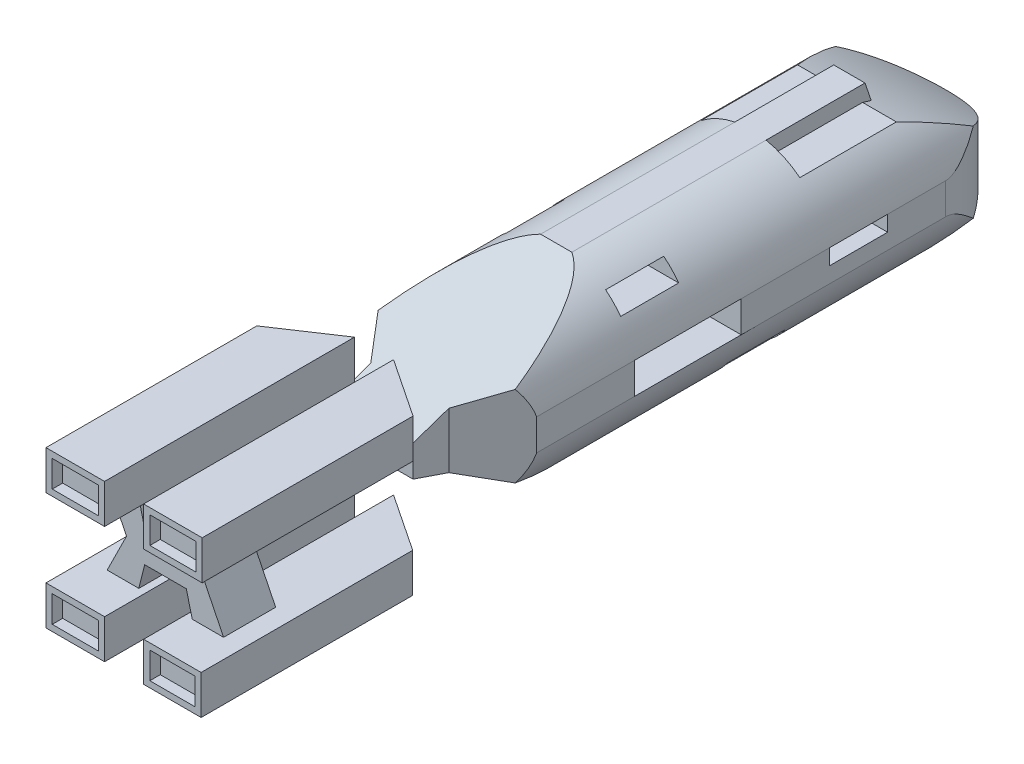
SolidWorks part; units mm, degrees
material "Ti-8Mn annealed sheet (SS)"
ref_plane "Front Plane" through (0, 0, 0) normal (0, 0, 1) x (1, 0, 0)
ref_plane "Top Plane" through (0, 0, 0) normal (0, 1, 0) x (1, 0, 0)
ref_plane "Right Plane" through (0, 0, 0) normal (1, 0, 0) x (0, 0, -1)
sketch "Sketch1" plane through (0, 0, 0) normal (0, 1, 0) x (1, 0, 0)
  line L1 (-75000, 375000) -> (75000, 375000)
  line L2 (-75000, 375000) -> (-75000, -375000)
  line L3 (-75000, -375000) -> (75000, -375000)
  line L4 (75000, 375000) -> (75000, -375000)
  line L5 (-75000, 375000) -> (75000, -375000) construction
  line L6 (-75000, -375000) -> (75000, 375000) construction
  point P0 (0, 0)
  dimension "D1" = 150000
  dimension "D2" = 750000
extrude "Boss-Extrude1" add sketch "Sketch1" along normal blind 150000
sketch "Sketch3" plane through (75000, 0, 0) normal (1, 0, 0) x (0, 0, -1)
  line L0 (0, -5407.3313) -> (0, 150000) construction
  line L1 (-375000, 150000) -> (375000, 150000) construction
  line L2 (187500, 150000) -> (375000, 150000)
  line L3 (375000, 150000) -> (375000, 90000)
  line L4 (187500, 150000) -> (187500, 0) construction
  line L5 (-375000, 0) -> (375000, 0) construction
  line L6 (375000, 60000) -> (375000, 0)
  line L7 (375000, 0) -> (187500, 0)
  line L8 (375000, 150000) -> (375000, 0) construction
  line L12 (187500, 150000) -> (187500, 0) construction
  line L19 (375000, 75000) -> (375000, 90000) construction
  line L20 (375000, 90000) -> (375000, 75000) construction
  line L21 (375000, 75000) -> (375000, 60000) construction
  arc A0 (375000, 90000) -> (187500, 150000) centre (175711.7775, -209806.9452) ccw
  arc A1 (375000, 60000) -> (187500, 0) centre (175711.7775, 359806.9452) cw
  dimension "D1" = 15000
  dimension "D2" = 15000
extrude "Cut-Extrude2" cut sketch "Sketch3" against normal through all
sketch "Sketch4" plane through (0, 150000, 0) normal (0, 1, 0) x (1, 0, 0)
  line L0 (0, 0) -> (0, -375000) construction
  line L1 (-75000, -375000) -> (75000, -375000) construction
  line L2 (0, -375000) -> (0, -187500) construction
  line L3 (0, -187500) -> (0, 0) construction
  line L4 (0, -187500) -> (-75000, -187500) construction
  line L5 (-75000, 187500) -> (-75000, -375000) construction
  line L6 (-75000, -187500) -> (75000, -187500) construction
  line L7 (75000, -375000) -> (75000, 187500) construction
  line L8 (75000, -187500) -> (75000, -93750) construction
  line L9 (75000, -93750) -> (-75000, -93750) construction
  line L10 (-75000, -93750) -> (-75000, -187500) construction
  line L11 (-37500, -187500) -> (-37500, -93750) construction
  line L12 (-37500, -93750) -> (0, -187500) construction
  line L13 (0, -187500) -> (75000, -187500) construction
  line L14 (75000, -187500) -> (37500, -187500) construction
  line L15 (37500, -187500) -> (37500, -93750) construction
  line L16 (37500, -93750) -> (0, -187500) construction
  line L17 (-75000, -93750) -> (-37500, -140625)
  line L18 (-37500, -140625) -> (-37500, -187500)
  line L19 (-37500, -187500) -> (-75000, -187500)
  line L20 (-75000, -187500) -> (-75000, -93750)
  line L21 (75000, -93750) -> (37500, -140625)
  line L22 (37500, -140625) -> (37500, -187500)
  line L23 (37500, -187500) -> (75000, -187500)
  line L24 (75000, -187500) -> (75000, -93750)
extrude "Cut-Extrude3" cut sketch "Sketch4" against normal through all
sketch "Sketch5" plane through (0, 0, 375000) normal (0, 0, 1) x (1, 0, 0)
  line L0 (0, 0) -> (0, 150000) construction
  line L1 (-75000, 0) -> (75000, 0) construction
  line L2 (-75000, 150000) -> (75000, 150000) construction
  line L3 (0, 150000) -> (0, 75000) construction
  line L4 (0, 75000) -> (75000, 150000) construction
  line L5 (75000, 150000) -> (75000, 75000) construction
  line L6 (75000, 150000) -> (75000, 0) construction
  line L7 (75000, 75000) -> (75000, 0) construction
  line L8 (75000, 0) -> (0, 75000) construction
  line L9 (0, 75000) -> (-75000, 150000) construction
  line L10 (-75000, 150000) -> (-75000, 75000) construction
  line L11 (-75000, 150000) -> (-75000, 0) construction
  line L12 (-75000, 75000) -> (-75000, 0) construction
  line L13 (-75000, 0) -> (0, 75000) construction
  line L14 (-37500, 112500) -> (0, 112500) construction
  line L15 (0, 112500) -> (37500, 112500) construction
  line L16 (37500, 112500) -> (18750, 112500) construction
  line L17 (18750, 112500) -> (18750, 0) construction
  line L18 (18750, 0) -> (-18750, 0) construction
  line L19 (-18750, 0) -> (-18750, 112500) construction
  line L20 (-75000, 150000) -> (-18750, 150000)
  line L21 (-75000, 150000) -> (-75000, 112500)
  line L22 (-18750, 150000) -> (-18750, 112500)
  line L23 (-75000, 112500) -> (-18750, 112500)
  line L24 (18750, 112500) -> (75000, 112500)
  line L25 (18750, 112500) -> (18750, 150000)
  line L26 (75000, 112500) -> (75000, 150000)
  line L27 (18750, 150000) -> (75000, 150000)
  line L28 (-75000, 37500) -> (-75000, 0)
  line L29 (-75000, 37500) -> (-18750, 37500)
  line L30 (-75000, 0) -> (-18750, 0)
  line L31 (-18750, 37500) -> (-18750, 0)
  line L32 (18750, 0) -> (18750, 37500)
  line L33 (18750, 0) -> (73969.9506, 0)
  line L34 (18750, 37500) -> (73969.9506, 37500)
  line L35 (73969.9506, 0) -> (73969.9506, 37500)
extrude "Cut-Extrude4" cut sketch "Sketch5" against normal blind 200000 flip side to cut
sketch "Sketch6" plane through (0, 0, 375000) normal (0, 0, 1) x (1, 0, 0)
  line L0 (60164.9629, 28125) -> (37113.7315, 75000)
  line L1 (-75000, 112500) -> (-75000, 37500) construction
  line L2 (-37628.7562, 75000) -> (-60937.5, 121875)
  line L3 (-18750, 0) -> (18750, 0) construction
  line L4 (-60937.5, 121875) -> (-32812.5, 140625)
  line L5 (73969.9506, 37500) -> (75000, 112500) construction
  line L6 (-37628.7562, 75000) -> (-60937.5, 28125)
  line L7 (37113.7315, 75000) -> (60937.5, 121875)
  line L8 (-75000, 75000) -> (-257.5124, 75000) construction
  line L10 (-46875, 131250) -> (46359.9753, 18750) construction
  line L11 (-257.5124, 75000) -> (-37628.7562, 75000) construction
  line L12 (-37628.7562, 75000) -> (-257.5124, 75000) construction
  line L13 (-257.5124, 75000) -> (74484.9753, 75000) construction
  line L14 (74484.9753, 75000) -> (37113.7315, 75000) construction
  line L15 (37113.7315, 75000) -> (-257.5124, 75000) construction
  line L16 (-18750, 150000) -> (-46875, 131250) construction
  line L17 (-46875, 131250) -> (-75000, 112500) construction
  line L18 (-75000, 112500) -> (-75000, 75000) construction
  line L19 (-75000, 75000) -> (-75000, 37500) construction
  line L20 (-75000, 37500) -> (-46875, 18750) construction
  line L21 (-46875, 18750) -> (-18750, 0) construction
  line L22 (-18750, 0) -> (18750, 0) construction
  line L23 (18750, 0) -> (46359.9753, 18750) construction
  line L24 (46359.9753, 18750) -> (73969.9506, 37500) construction
  line L25 (73969.9506, 37500) -> (74484.9753, 75000) construction
  line L26 (74484.9753, 75000) -> (75000, 112500) construction
  line L27 (75000, 112500) -> (46875, 131250) construction
  line L28 (46875, 131250) -> (18750, 150000) construction
  line L30 (-32812.5, 140625) -> (-20257.5124, 90000)
  line L31 (-20257.5124, 90000) -> (19742.4876, 90000)
  line L33 (-20257.5124, 60000) -> (19742.4876, 60000)
  line L35 (-20257.5124, 90000) -> (19742.4876, 60000) construction
  line L36 (-20257.5124, 60000) -> (19742.4876, 90000) construction
  line L38 (19742.4876, 90000) -> (32812.5, 140625)
  line L39 (32812.5, 140625) -> (60937.5, 121875)
  line L40 (60164.9629, 28125) -> (32554.9876, 9375)
  line L41 (32554.9876, 9375) -> (19742.4876, 60000)
  line L42 (-20257.5124, 60000) -> (-32812.5, 9375)
  line L43 (-32812.5, 9375) -> (-60937.5, 28125)
  dimension "D1" = 40000
  dimension "D2" = 30000
extrude "Boss-Extrude2" add sketch "Sketch6" against normal blind 50000
sketch "Sketch7" plane through (0, 0, 375000) normal (0, 0, 1) x (1, 0, 0)
  line L0 (-20257.5124, 90000) -> (-37628.7562, 75000)
  line L1 (-37628.7562, 75000) -> (-20257.5124, 60000)
  line L2 (-20257.5124, 60000) -> (19742.4876, 60000)
  line L3 (19742.4876, 60000) -> (37113.7315, 75000)
  line L4 (37113.7315, 75000) -> (19742.4876, 90000)
  line L5 (19742.4876, 90000) -> (-20257.5124, 90000)
extrude "Boss-Extrude3" add sketch "Sketch7" against normal blind 280000
sketch "Sketch8" plane through (75000, 0, 0) normal (1, 0, 0) x (0, 0, -1)
  line L0 (0, 150000) -> (-175000, 90000)
  line L1 (-93750, 150000) -> (187500, 150000) construction
  line L2 (-175000, 90000) -> (-175000, 150000)
  line L3 (-140625, 150000) -> (-187500, 150000) construction
  line L4 (-175000, 150000) -> (0, 150000)
  line L5 (0, 0) -> (-175000, 60000)
  line L6 (-175000, 60000) -> (-175000, 0)
  line L7 (-175000, 0) -> (0, 0)
extrude "Cut-Extrude5" cut sketch "Sketch8" against normal through all
sketch "Sketch9" plane through (0, 150000, 0) normal (0, 1, 0) x (1, 0, 0)
  line L0 (-18750, -175000) -> (-37500, -187500)
  line L1 (-37500, -187500) -> (-75000, -212500)
  line L3 (-75000, -187500) -> (-75000, -375000) construction
  line L7 (18750, -175000) -> (37500, -187500)
  line L8 (18750, -175000) -> (18750, -375000) construction
  line L9 (37500, -187500) -> (75000, -212500)
  line L10 (75000, -375000) -> (75000, -187500) construction
  line L13 (-75000, -212500) -> (-75000, -175000)
  line L14 (-75000, -175000) -> (-18750, -175000)
  line L15 (18750, -175000) -> (75000, -175000)
  line L16 (75000, -175000) -> (75000, -212500)
extrude "Cut-Extrude7" cut sketch "Sketch9" against normal blind 38976
sketch "Sketch10" plane through (0, 0, -375000) normal (0, 0, -1) x (-1, 0, 0)
  line L0 (-75000, 90000) -> (75000, 60000) construction
  circle A0 centre (0, 75000) radius 76485.2927
extrude "Cut-Extrude8" cut sketch "Sketch10" against normal blind 496230 flip side to cut
sketch "Sketch11" plane through (0, 0, 0) normal (0, -1, 0) x (1, 0, 0)
  line L0 (-18750, 175000) -> (-37500, 187500)
  line L1 (-37500, 187500) -> (-75000, 212500)
  line L2 (-75000, 187500) -> (-75000, 375000) construction
  line L3 (-18750, 175000) -> (-75000, 175000)
  line L4 (-75000, 175000) -> (-75000, 212500)
  line L5 (18750, 175000) -> (37500, 187500)
  line L6 (18750, 175000) -> (37500, 175000) construction
  line L7 (37500, 187500) -> (73969.9506, 211813.3004)
  line L8 (73969.9506, 187500) -> (73969.9506, 375000) construction
  line L9 (18750, 175000) -> (73969.9506, 175000)
  line L10 (73969.9506, 175000) -> (73969.9506, 211813.3004)
extrude "Cut-Extrude10" cut sketch "Sketch11" against normal blind 40000
sketch "Sketch14" plane through (0, 0, 375000) normal (0, 0, 1) x (1, 0, 0)
  line L1 (73969.9506, 0) -> (18750, 0)
  line L2 (73969.9506, 0) -> (73969.9506, 37500)
  line L3 (73969.9506, 37500) -> (18750, 37500)
  line L4 (18750, 0) -> (18750, 37500)
  line L5 (-18750, 0) -> (-75000, 0)
  line L6 (-18750, 0) -> (-18750, 37500)
  line L7 (-18750, 37500) -> (-75000, 37500)
  line L8 (-75000, 0) -> (-75000, 37500)
  line L9 (-18750, 112500) -> (-75000, 112500)
  line L10 (-18750, 112500) -> (-18750, 150000)
  line L11 (-18750, 150000) -> (-75000, 150000)
  line L12 (-75000, 112500) -> (-75000, 150000)
  line L13 (75000, 112500) -> (18750, 112500)
  line L14 (75000, 112500) -> (75000, 150000)
  line L15 (75000, 150000) -> (18750, 150000)
  line L16 (18750, 112500) -> (18750, 150000)
extrude "Boss-Extrude5" add sketch "Sketch14" along normal blind 40000
sketch "Sketch15" plane through (0, 0, 0) normal (0, -1, 0) x (1, 0, 0)
  line L0 (0, -187500) -> (0, -375000) construction
  line L1 (-15000, -187500) -> (15000, -187500) construction
  line L2 (-75000, -375000) -> (75000, -375000) construction
  line L3 (0, -375000) -> (0, -299000) construction
  line L4 (0, -299000) -> (-75000, -299000) construction
  line L5 (-75000, 93750) -> (-75000, -375000) construction
  line L6 (-75000, -299000) -> (0, -299000) construction
  line L7 (0, -299000) -> (75000, -299000) construction
  line L8 (75000, -375000) -> (75000, 93750) construction
  line L9 (-75000, -299000) -> (-75000, -375000)
  line L10 (-75000, -375000) -> (75000, -375000)
  line L11 (75000, -375000) -> (75000, -299000)
  arc A0 (-75000, -299000) -> (75000, -299000) centre (0, -299000) ccw
  dimension "D1" = 76000
extrude "Cut-Extrude12" cut sketch "Sketch15" against normal through all
sketch "Sketch20" plane through (-75000, 0, 0) normal (-1, 0, 0) x (0, 0, 1)
  line L0 (-102625, 90000) -> (-102625, 60000) construction
  line L1 (-299000, 90000) -> (93750, 90000) construction
  line L2 (93750, 60000) -> (-299000, 60000) construction
  line L3 (-187500, 75000) -> (-187500, 90000) construction
  line L4 (-102625, 150000) -> (-102625, 0) construction
  line L5 (-187500, 150000) -> (0, 150000) construction
  line L6 (-187500, 0) -> (0, 0) construction
  line L7 (-102625, 0) -> (0, 0) construction
  line L8 (0, 0) -> (0, 150000) construction
  line L9 (0, 150000) -> (-187500, 150000) construction
  line L10 (-187500, 150000) -> (-187500, 0) construction
  line L11 (-187500, 0) -> (-187500, 75000) construction
  line L12 (-187500, 75000) -> (-299000, 75000) construction
  line L13 (-299000, 90000) -> (-299000, 60000) construction
  line L14 (-102625, 90000) -> (0, 90000)
  line L15 (-102625, 90000) -> (-102625, 60000)
  line L16 (-102625, 60000) -> (0, 60000)
  line L17 (0, 90000) -> (0, 60000)
  line L19 (-187500, 90000) -> (-243250, 90000)
  line L20 (-187500, 90000) -> (-187500, 75000)
  line L21 (-187500, 75000) -> (-243250, 75000)
  line L22 (-243250, 90000) -> (-243250, 75000)
extrude "Cut-Extrude15" cut sketch "Sketch20" against normal blind 20000
sketch "Sketch21" plane through (-55000, 0, 0) normal (-1, 0, 0) x (0, 0, 1)
  line L8 (-102625, 90000) -> (-102625, 60000)
  line L9 (-102625, 60000) -> (0, 60000)
  line L10 (0, 60000) -> (0, 90000)
  line L11 (0, 90000) -> (-102625, 90000)
  line L12 (-102625, 90000) -> (-102625, 60000)
  line L13 (-102625, 60000) -> (0, 60000)
  line L14 (0, 60000) -> (0, 90000)
  line L15 (0, 90000) -> (-102625, 90000)
  dimension "D1" = 0
extrude "Cut-Extrude16" cut sketch "Sketch21" against normal through all
sketch "Sketch22" plane through (0, 150000, 0) normal (0, 1, 0) x (1, 0, 0)
  line L0 (-15000, 187500) -> (-15000, 287500) construction
  line L2 (15000, 187500) -> (-15000, 187500)
  line L3 (15000, 187500) -> (15000, 287500)
  line L4 (15000, 287500) -> (-15000, 287500)
  line L5 (-15000, 187500) -> (-15000, 287500)
  dimension "D1" = 100000
extrude "Boss-Extrude8" add sketch "Sketch22" against normal blind 39634
sketch "Sketch23" plane through (-15000, 0, 0) normal (-1, 0, 0) x (0, 0, 1)
  line L0 (-287500, 132396.7855) -> (-287500, 150000)
  line L1 (-287500, 150000) -> (-281500, 150000)
  line L2 (-287500, 150000) -> (-187500, 150000) construction
  line L3 (-281500, 150000) -> (-287500, 132396.7855)
  dimension "D1" = 6000
extrude "Cut-Extrude17" cut sketch "Sketch23" against normal blind 39634
sketch "Sketch24" plane through (-75000, 0, 0) normal (-1, 0, 0) x (0, 0, 1)
  line L0 (-102625, 60000) -> (-102625, 0) construction
  line L1 (-187500, 0) -> (0, 0) construction
  line L2 (-102625, 0) -> (-102625, 150000) construction
  line L3 (-187500, 150000) -> (0, 150000) construction
  line L4 (-102625, 150000) -> (0, 150000) construction
  line L5 (0, 150000) -> (0, 0) construction
  line L6 (0, 0) -> (0, 75000) construction
  line L9 (-243250, 75000) -> (-187500, 75000) construction
  line L10 (-187500, 75000) -> (-187500, 90000) construction
  line L11 (0, 90000) -> (0, 150000) construction
  line L12 (-102625, 30000) -> (-158375, 30000)
  line L13 (-102625, 30000) -> (-102625, 15000)
  line L14 (-102625, 15000) -> (-158375, 15000)
  line L15 (-158375, 30000) -> (-158375, 15000)
  line L17 (0, 120000) -> (-55750, 120000)
  line L18 (0, 120000) -> (0, 135000)
  line L19 (0, 135000) -> (-55750, 135000)
  line L20 (-55750, 120000) -> (-55750, 135000)
  dimension "D1" = 55750
  dimension "D2" = 15000
  dimension "D3" = 55750
  dimension "D4" = 15000
  dimension "D5" = 55750
  dimension "D6" = 15000
extrude "Cut-Extrude18" cut sketch "Sketch24" against normal blind 55000
mirror "Mirror1" about plane through (0, 0, 0) normal (1, 0, 0) of "Cut-Extrude15", "Cut-Extrude17", "Cut-Extrude18"
sketch "Sketch25" plane through (0, 150000, 0) normal (0, 1, 0) x (1, 0, 0)
  line L1 (15000, 281500) -> (60000, 281500)
  line L2 (15000, 281500) -> (15000, 186500)
  line L3 (15000, 186500) -> (60000, 186500)
  line L4 (60000, 281500) -> (60000, 186500)
  line L5 (-15000, 281500) -> (-60000, 281500)
  line L6 (-15000, 281500) -> (-15000, 186500)
  line L7 (-15000, 186500) -> (-60000, 186500)
  line L8 (-60000, 281500) -> (-60000, 186500)
  dimension "D1" = 95000
  dimension "D2" = 45000
  dimension "D3" = 45000
  dimension "D4" = 95000
extrude "Cut-Extrude19" cut sketch "Sketch25" against normal blind 15000
sketch "Sketch27" plane through (0, 0, 0) normal (0, -1, 0) x (1, 0, 0)
  line L0 (-65836.5965, 105204.2544) -> (-65836.5965, 0) construction
  line L1 (-65836.5965, 0) -> (0, 0) construction
  line L2 (0, 0) -> (-65836.5965, 105204.2544) construction
  line L3 (-65836.5965, 105204.2544) -> (65836.5965, 105204.2544) construction
  line L4 (65836.5965, 105204.2544) -> (65836.5965, 0) construction
  line L5 (65836.5965, 0) -> (0, 0) construction
  line L6 (0, 0) -> (65836.5965, 105204.2544) construction
  line L7 (-32918.2983, 52602.1272) -> (-32918.2983, 0) construction
  line L8 (-32918.2983, 0) -> (-32918.2983, 52602.1272) construction
  line L9 (-32918.2983, 52602.1272) -> (32918.2983, 52602.1272) construction
  line L10 (32918.2983, 52602.1272) -> (32918.2983, 0) construction
  line L12 (-32918.2983, 0) -> (32918.2983, 0)
  line L13 (-32918.2983, 0) -> (-32918.2983, 105204.2544)
  line L14 (-32918.2983, 105204.2544) -> (32918.2983, 105204.2544)
  line L15 (32918.2983, 0) -> (32918.2983, 105204.2544)
extrude "Cut-Extrude22" cut sketch "Sketch27" against normal blind 50000
sketch "Sketch31" plane through (0, 0, 415000) normal (0, 0, 1) x (1, 0, 0)
  line L8 (-24750, 118500) -> (-24750, 144000)
  line L9 (-24750, 144000) -> (-69000, 144000)
  line L10 (-69000, 144000) -> (-69000, 118500)
  line L11 (-69000, 118500) -> (-24750, 118500)
  line L12 (-24750, 118500) -> (-24750, 144000)
  line L13 (-24750, 144000) -> (-69000, 144000)
  line L14 (-69000, 144000) -> (-69000, 118500)
  line L15 (-69000, 118500) -> (-24750, 118500)
  line L20 (69000, 118500) -> (69000, 144000)
  line L21 (69000, 144000) -> (24750, 144000)
  line L22 (24750, 144000) -> (24750, 118500)
  line L23 (24750, 118500) -> (69000, 118500)
  line L24 (69000, 118500) -> (69000, 144000)
  line L25 (69000, 144000) -> (24750, 144000)
  line L26 (24750, 144000) -> (24750, 118500)
  line L27 (24750, 118500) -> (69000, 118500)
  line L32 (-24750, 6000) -> (-24750, 31500)
  line L33 (-24750, 31500) -> (-69000, 31500)
  line L34 (-69000, 31500) -> (-69000, 6000)
  line L35 (-69000, 6000) -> (-24750, 6000)
  line L36 (-24750, 6000) -> (-24750, 31500)
  line L37 (-24750, 31500) -> (-69000, 31500)
  line L38 (-69000, 31500) -> (-69000, 6000)
  line L39 (-69000, 6000) -> (-24750, 6000)
  line L44 (67969.9506, 6000) -> (67969.9506, 31500)
  line L45 (67969.9506, 31500) -> (24750, 31500)
  line L46 (24750, 31500) -> (24750, 6000)
  line L47 (24750, 6000) -> (67969.9506, 6000)
  line L48 (67969.9506, 6000) -> (67969.9506, 31500)
  line L49 (67969.9506, 31500) -> (24750, 31500)
  line L50 (24750, 31500) -> (24750, 6000)
  line L51 (24750, 6000) -> (67969.9506, 6000)
  dimension "D1" = 6000
  dimension "D2" = 6000
  dimension "D3" = 6000
  dimension "D4" = 6000
extrude "Cut-Extrude24" cut sketch "Sketch31" against normal up to vertex (240000 mm away) up to point (19742.4876, 90000, 175000)
sketch "Sketch32" [suppressed] plane through (0, 0, -243250) normal (0, 0, 1) x (1, 0, 0)
  line L0 (-55000, 90000) -> (-75000, 75000) construction
  line L1 (75000, 90000) -> (55000, 75000) construction
  circle A0 centre (-65000, 82500) radius 5000
  circle A1 centre (65000, 82500) radius 5000
  dimension "D1" = 10000
  dimension "D2" = 10000
extrude "Boss-Extrude11" [suppressed] add sketch "Sketch32" against normal blind 120000
sketch "Sketch33" plane through (0, 0, 415000) normal (0, 0, 1) x (1, 0, 0)
  line L8 (-24750, 118500) -> (-24750, 144000)
  line L9 (-69000, 118500) -> (-24750, 118500)
  line L10 (-69000, 144000) -> (-69000, 118500)
  line L11 (-24750, 144000) -> (-69000, 144000)
  line L12 (-24750, 118500) -> (-24750, 144000)
  line L13 (-69000, 118500) -> (-24750, 118500)
  line L14 (-69000, 144000) -> (-69000, 118500)
  line L15 (-24750, 144000) -> (-69000, 144000)
  line L20 (24750, 118500) -> (69000, 118500)
  line L21 (69000, 118500) -> (69000, 144000)
  line L22 (69000, 144000) -> (24750, 144000)
  line L23 (24750, 144000) -> (24750, 118500)
  line L24 (24750, 118500) -> (69000, 118500)
  line L25 (69000, 118500) -> (69000, 144000)
  line L26 (69000, 144000) -> (24750, 144000)
  line L27 (24750, 144000) -> (24750, 118500)
  line L32 (-24750, 6000) -> (-24750, 31500)
  line L33 (-69000, 6000) -> (-24750, 6000)
  line L34 (-69000, 31500) -> (-69000, 6000)
  line L35 (-24750, 31500) -> (-69000, 31500)
  line L36 (-24750, 6000) -> (-24750, 31500)
  line L37 (-69000, 6000) -> (-24750, 6000)
  line L38 (-69000, 31500) -> (-69000, 6000)
  line L39 (-24750, 31500) -> (-69000, 31500)
  line L44 (24750, 6000) -> (67969.9506, 6000)
  line L45 (67969.9506, 6000) -> (67969.9506, 31500)
  line L46 (67969.9506, 31500) -> (24750, 31500)
  line L47 (24750, 31500) -> (24750, 6000)
  line L48 (24750, 6000) -> (67969.9506, 6000)
  line L49 (67969.9506, 6000) -> (67969.9506, 31500)
  line L50 (67969.9506, 31500) -> (24750, 31500)
  line L51 (24750, 31500) -> (24750, 6000)
  dimension "D1" = 0
  dimension "D2" = 0
  dimension "D3" = 0
  dimension "D4" = 0
extrude "Boss-Extrude12" add sketch "Sketch33" against normal blind 200000
sketch "Sketch34" plane through (0, 0, 415000) normal (0, 0, 1) x (1, 0, 0)
  line L8 (-24750, 118500) -> (-24750, 144000)
  line L9 (-24750, 144000) -> (-69000, 144000)
  line L10 (-69000, 144000) -> (-69000, 118500)
  line L11 (-69000, 118500) -> (-24750, 118500)
  line L12 (-24750, 118500) -> (-24750, 144000)
  line L13 (-24750, 144000) -> (-69000, 144000)
  line L14 (-69000, 144000) -> (-69000, 118500)
  line L15 (-69000, 118500) -> (-24750, 118500)
  line L20 (69000, 118500) -> (69000, 144000)
  line L21 (69000, 144000) -> (24750, 144000)
  line L22 (24750, 144000) -> (24750, 118500)
  line L23 (24750, 118500) -> (69000, 118500)
  line L24 (69000, 118500) -> (69000, 144000)
  line L25 (69000, 144000) -> (24750, 144000)
  line L26 (24750, 144000) -> (24750, 118500)
  line L27 (24750, 118500) -> (69000, 118500)
  line L32 (-24750, 6000) -> (-24750, 31500)
  line L33 (-24750, 31500) -> (-69000, 31500)
  line L34 (-69000, 31500) -> (-69000, 6000)
  line L35 (-69000, 6000) -> (-24750, 6000)
  line L36 (-24750, 6000) -> (-24750, 31500)
  line L37 (-24750, 31500) -> (-69000, 31500)
  line L38 (-69000, 31500) -> (-69000, 6000)
  line L39 (-69000, 6000) -> (-24750, 6000)
  line L44 (67969.9506, 6000) -> (67969.9506, 31500)
  line L45 (67969.9506, 31500) -> (24750, 31500)
  line L46 (24750, 31500) -> (24750, 6000)
  line L47 (24750, 6000) -> (67969.9506, 6000)
  line L48 (67969.9506, 6000) -> (67969.9506, 31500)
  line L49 (67969.9506, 31500) -> (24750, 31500)
  line L50 (24750, 31500) -> (24750, 6000)
  line L51 (24750, 6000) -> (67969.9506, 6000)
  dimension "D1" = 6000
  dimension "D2" = 6000
  dimension "D3" = 6000
  dimension "D4" = 6000
extrude "Cut-Extrude25" cut sketch "Sketch34" against normal blind 10000
sketch "Sketch35" plane through (0, 0, 0) normal (0, -1, 0) x (1, 0, 0)
  line L0 (-15000, -187500) -> (-15000, -307500) construction
  line L2 (15000, -187500) -> (-15000, -187500)
  line L3 (15000, -187500) -> (15000, -307500)
  line L4 (15000, -307500) -> (-15000, -307500)
  line L5 (-15000, -187500) -> (-15000, -307500)
  dimension "D1" = 120000
extrude "Cut-Extrude26" cut sketch "Sketch35" against normal blind 20000
sketch "Sketch36" plane through (0, 0, -187500) normal (0, 0, -1) x (-1, 0, 0)
  line L0 (0, 0) -> (-15000, 20000) construction
  line L1 (15000, 0) -> (-15000, 0) construction
  line L2 (-15000, 20000) -> (15000, 20000) construction
  line L3 (15000, 20000) -> (0, 0) construction
  circle A0 centre (7500, 10000) radius 5000
  circle A1 centre (-7500, 10000) radius 5000
  dimension "D1" = 10000
  dimension "D2" = 10000
extrude "Boss-Extrude13" add sketch "Sketch36" along normal blind 67198
sketch "Sketch37" plane through (0, 0, -254698) normal (0, 0, -1) x (-1, 0, 0)
  line L1 (-12500, 15000) -> (-2500, 15000)
  line L2 (-12500, 15000) -> (-12500, 5000)
  line L3 (-12500, 5000) -> (-2500, 5000)
  line L4 (-2500, 15000) -> (-2500, 5000)
  line L5 (-12500, 15000) -> (-2500, 5000) construction
  line L6 (-12500, 5000) -> (-2500, 15000) construction
  line L7 (2500, 15000) -> (12500, 15000)
  line L8 (2500, 15000) -> (2500, 5000)
  line L9 (2500, 5000) -> (12500, 5000)
  line L10 (12500, 15000) -> (12500, 5000)
  line L11 (2500, 15000) -> (12500, 5000) construction
  line L12 (2500, 5000) -> (12500, 15000) construction
  point P0 (-7500, 10000)
  point P6 (7500, 10000)
  dimension "D1" = 10000
  dimension "D2" = 10000
  dimension "D3" = 10000
  dimension "D4" = 10000
extrude "Boss-Extrude14" add sketch "Sketch37" along normal blind 11113
sketch "Sketch38" plane through (0, 0, -265811) normal (0, 0, -1) x (-1, 0, 0)
  line L0 (12500, 15000) -> (2500, 5000) construction
  line L1 (2500, 5000) -> (12500, 5000) construction
  line L2 (-12500, 15000) -> (-2500, 5000) construction
  circle A0 centre (-7500, 10000) radius 4000
  circle A1 centre (7500, 10000) radius 4000
  dimension "D1" = 8000
  dimension "D2" = 8000
extrude "Cut-Extrude27" cut sketch "Sketch38" against normal blind 86238
sketch "Sketch39" plane through (0, 101574.3149, -298005.7417) normal (0, 0.3226, -0.9465) x (-1, 0, 0)
  line L0 (0, 51161.3769) -> (0, 32563.7115) construction
  line L1 (-15000, 51161.3769) -> (15000, 51161.3769) construction
  line L2 (15000, 32563.7115) -> (-15000, 32563.7115) construction
  line L3 (0, 32563.7115) -> (0, 41862.5442) construction
  line L4 (0, 41862.5442) -> (15000, 41862.5442) construction
  line L5 (15000, 32563.7115) -> (15000, 51161.3769) construction
  line L6 (15000, 41862.5442) -> (-15000, 41862.5442) construction
  line L7 (-15000, 51161.3769) -> (-15000, 32563.7115) construction
  line L8 (-15000, 41862.5442) -> (-15000, 51161.3769) construction
  line L9 (-15000, 51161.3769) -> (-15000, 46511.9606) construction
  line L10 (-15000, 46511.9606) -> (15000, 46511.9606) construction
  line L11 (15000, 46511.9606) -> (7500, 41862.5442) construction
  line L12 (7500, 41862.5442) -> (0, 46511.9606) construction
  line L13 (0, 46511.9606) -> (3750, 44187.2524) construction
  line L14 (0, 46511.9606) -> (0, 41862.5442) construction
  line L15 (0, 41862.5442) -> (-15000, 41862.5442) construction
  line L16 (-15000, 41862.5442) -> (-7500, 41862.5442) construction
  line L17 (-7500, 41862.5442) -> (-15000, 46511.9606) construction
  line L18 (-15000, 46511.9606) -> (0, 46511.9606) construction
  line L19 (0, 46511.9606) -> (-7500, 41862.5442) construction
  line L20 (11250, 44187.2524) -> (3750, 44187.2524)
  line L21 (3750, 44187.2524) -> (7500, 41862.5442)
  line L22 (7500, 41862.5442) -> (11250, 44187.2524)
  line L24 (-3750, 44187.2524) -> (-11250, 44187.2524)
  line L25 (-11250, 44187.2524) -> (-7500, 41862.5442)
  line L26 (-7500, 41862.5442) -> (-3750, 44187.2524)
  line L27 (-7500, 41862.5442) -> (-3750, 41862.5442) construction
  line L28 (-3750, 41862.5442) -> (3750, 41862.5442) construction
  line L29 (3750, 41862.5442) -> (3750, 44187.2524) construction
  line L30 (-3750, 44187.2524) -> (3750, 44187.2524) construction
  line L31 (-3750, 41862.5442) -> (-3750, 44187.2524) construction
  line L32 (-3750, 43024.8983) -> (0, 43024.8983) construction
  line L33 (0, 43024.8983) -> (3750, 43024.8983) construction
  line L34 (-3750, 41862.5442) -> (0, 44187.2524)
  line L35 (0, 44187.2524) -> (3750, 41862.5442)
  line L36 (3750, 41862.5442) -> (-3750, 41862.5442)
extrude "Cut-Extrude28" cut sketch "Sketch39" against normal blind 10
